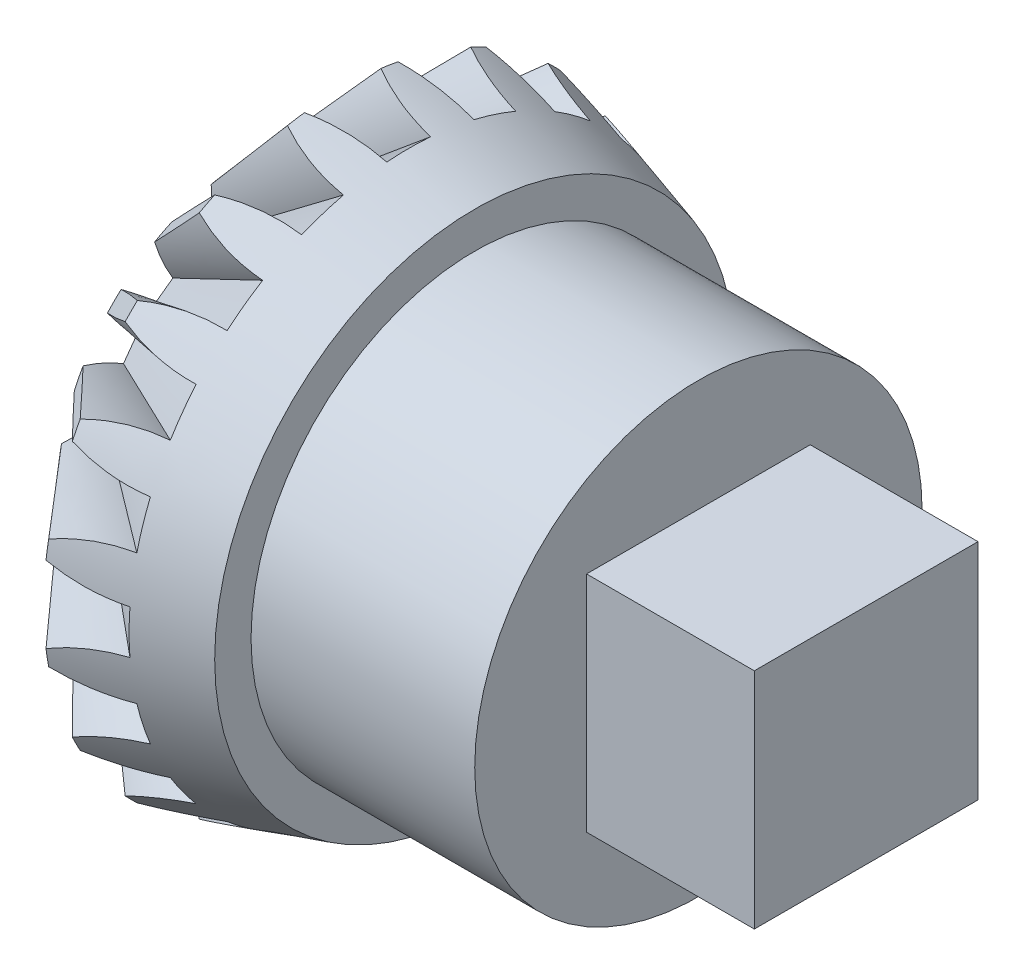
SolidWorks part; units mm, degrees
ref_plane "Front" through (0, 0, 0) normal (0, 0, 1) x (1, 0, 0)
ref_plane "Top" through (0, 0, 0) normal (0, 1, 0) x (1, 0, 0)
ref_plane "Right" through (0, 0, 0) normal (1, 0, 0) x (0, 0, -1)
sketch "Sketch1" plane through (0, 0, 0) normal (0, 0, 1) x (1, 0, 0)
  line L0 (0, 0) -> (8, 0) construction
  line L1 (0, 1.5) -> (8, 1.5)
  line L2 (8, 1.5) -> (8, 4)
  line L3 (8, 4) -> (4, 4)
  line L4 (4, 4) -> (4, 4.65)
  line L5 (4, 4.65) -> (1.6397, 5.35)
  line L6 (1.6397, 5.35) -> (0, 3.4628)
  line L7 (0, 3.4628) -> (0, 1.5)
  line L8 (2.8199, 5) -> (0, 1.7546) construction
  dimension "D1" = 49.013
  dimension "Overall Length" = 8
  dimension "OD" = 10.7
  dimension "For Shaft" = 3
  dimension "Face Width" = 2.5
  dimension "Hub Dia" = 8
  dimension "Hub Width" = 4
  dimension "PD" = 10
revolve "Revolve1" add sketch "Sketch1" angle 360 about L0
sketch "Sketch2" plane through (0, 0, 0) normal (-1, 0, 0) x (0, 0, 1)
  circle A0 centre (0, 0) radius 5
  dimension "Pitch Dia" = 10
sketch "Sketch3" plane through (0, 0, 0) normal (-1, 0, 0) x (0, 0, 1)
  line L0 (-10, 0) -> (10, 0) construction
  point P2 (0, 0)
  dimension "teeth" = 20
sketch "Sketch5" plane through (0, 0, 0) normal (-1, 0, 0) x (0, 0, 1)
  line L0 (0, 0) -> (0, 5.35) construction
  line L1 (0, 0) -> (0.4198, 5.3335) construction
  line L2 (0, 0) -> (-0.4198, 5.3335) construction
  line L4 (-10, 0) -> (10, 0) construction
  line L5 (-0.2099, 2.6668) -> (0.2099, 2.6668)
  line L6 (0, 0) -> (-1.6532, 5.0882) construction
  line L7 (0, 0) -> (1.6532, 5.0882) construction
  circle A0 centre (0, 0) radius 5.35 construction
  arc A1 (-0.2099, 2.6668) -> (-1.6532, 5.0882) centre (-3.3814, 2.4172) ccw
  arc A2 (0.2099, 2.6668) -> (1.6532, 5.0882) centre (3.3814, 2.4172) cw
  arc A3 (-1.6532, 5.0882) -> (1.6532, 5.0882) centre (0, 0) cw
  point P10 (0, 0)
  dimension "D1" = 9
  dimension "D2" = 36
ref_plane "Plane1" through (2.8199, 0, 0) normal (1, 0, 0) x (0, 0, -1)
sketch "Sketch6" plane through (2.8199, 0, 0) normal (1, 0, 0) x (0, 0, -1)
  line L0 (0, 0) -> (0, 8.025) construction
  line L1 (0, 0) -> (0.4198, 5.3335) construction
  line L2 (0, 0) -> (-0.4198, 5.3335) construction
  line L3 (0, 0) -> (2.6075, 8.025) construction
  line L4 (0, 0) -> (-2.6075, 8.025) construction
  line L5 (2.6075, 8.025) -> (-2.6075, 8.025) construction
  line L6 (0, 5.35) -> (0, 0) construction
  line L7 (-2.6075, 8.025) -> (2.6075, 8.025)
  circle A0 centre (0, 0) radius 5.35 construction
  arc A1 (-0.3923, 4.9846) -> (-2.6075, 8.025) centre (-3.9732, 4.7028) ccw
  arc A2 (0.3923, 4.9846) -> (2.6075, 8.025) centre (3.9732, 4.7028) cw
  circle A3 centre (0, 0) radius 5 construction
  arc A4 (0.3923, 4.9846) -> (-0.3923, 4.9846) centre (0, 0) ccw
  dimension "D1" = 9
  dimension "D2" = 36
  dimension "D3" = 8.025
  dimension "D4" = 5.35
loft "Cut-Loft1" cut profiles "Sketch6", "Sketch5" connector at (2.8199, 8.025, -2.6075) connector at (0, 5.0882, -1.6532)
pattern_circular "CirPattern1" count 20 over 360 about axis through (0, 0, 0) along (-1, 0, 0) of "Cut-Loft1"
sketch "Sketch7" plane through (0, 0, 0) normal (-1, 0, 0) x (0, 0, 1)
  circle A0 centre (0, 0) radius 5
sketch "Sketch8"
  dimension "D1" = 11
sketch_block_instance "Block1-1"
sketch_block "Block1"
sketch "Sketch9" plane through (8, 0, 0) normal (1, 0, 0) x (0, 0, -1)
  line L1 (2, -2) -> (-2, -2)
  line L2 (2, -2) -> (2, 2)
  line L3 (2, 2) -> (-2, 2)
  line L4 (-2, -2) -> (-2, 2)
  dimension "D1" = 2
  dimension "D2" = 4
  dimension "D3" = 2
extrude "Boss-Extrude1" add sketch "Sketch9" along normal blind 3
sketch "Sketch10" plane through (0, 0, 0) normal (-1, 0, 0) x (0, 0, 1)
  circle A0 centre (0, 0) radius 1.5 construction
  circle A1 centre (0, 0) radius 1.5
extrude "Boss-Extrude2" add sketch "Sketch10" against normal up to next
equation "\"D1@Sketch5\"=(360deg/20)/2"
equation "\"D2@Sketch5\"=(360deg/20)/.5"
equation "\"D1@Sketch6\"=(360deg/\"teeth@Sketch5\")/2"
equation "\"D2@Sketch6\"=(360deg/\"teeth@Sketch5\")/.5"
equation "\"D3@Sketch6\"=\"D4@Sketch6\"*1.5"
equation "\"D1@Sketch8\"=\"Mounting Distance@Sketch8\""
